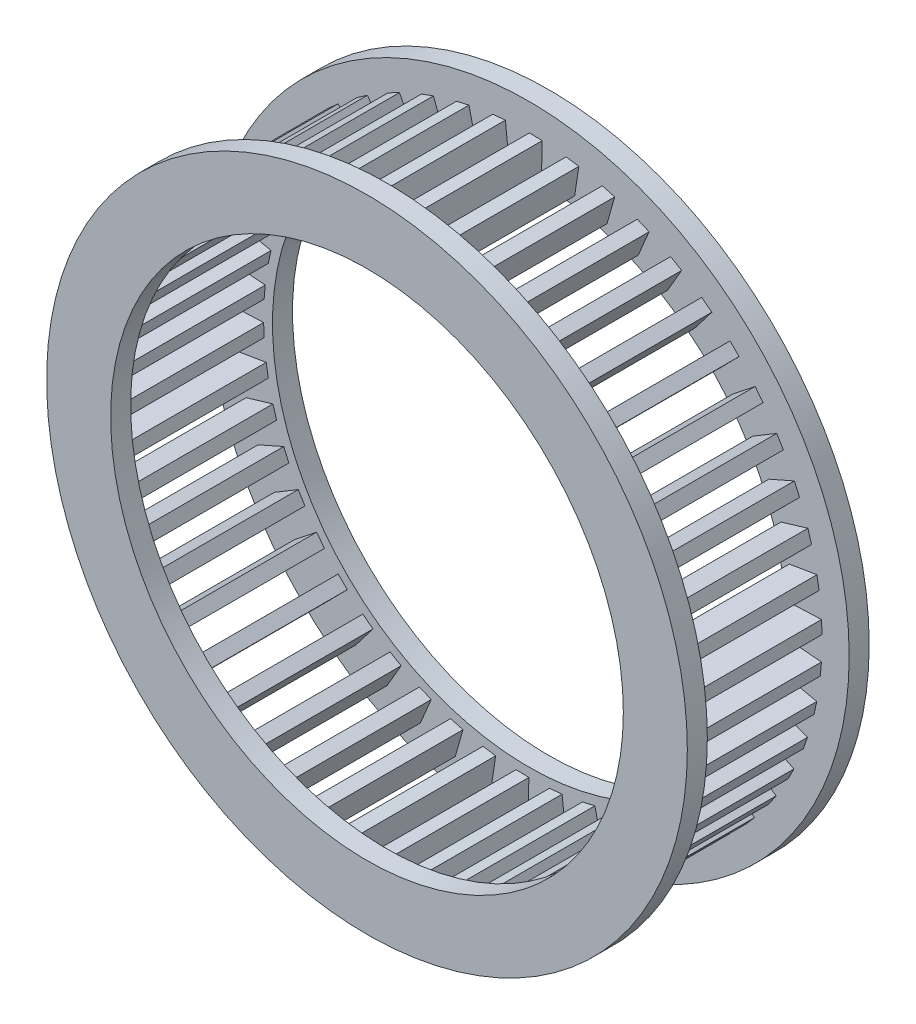
SolidWorks part; units mm, degrees
ref_plane "Спереди" through (0, 0, 0) normal (0, 0, 1) x (1, 0, 0)
ref_plane "Сверху" through (0, 0, 0) normal (0, 1, 0) x (1, 0, 0)
ref_plane "Справа" through (0, 0, 0) normal (1, 0, 0) x (0, 0, -1)
sketch "Эскиз1" plane through (0, 0, 0) normal (0, 0, 1) x (1, 0, 0)
  line L0 (56.0871, 0.8311) -> (62.0057, 1.0618)
  line L1 (62.0057, 1.0618) -> (61.9002, 3.7675)
  line L2 (61.9002, 3.7675) -> (55.9817, 3.5368)
  line L3 (55.9817, 3.5368) -> (56.0871, 0.8311)
  line L4 (55.5407, 7.8542) -> (61.3837, 8.8248)
  line L5 (61.3837, 8.8248) -> (60.9399, 11.4959)
  line L6 (60.9399, 11.4959) -> (55.0969, 10.5253)
  line L7 (55.0969, 10.5253) -> (55.5407, 7.8542)
  line L8 (54.1183, 14.7533) -> (59.7936, 16.4487)
  line L9 (59.7936, 16.4487) -> (59.0186, 19.0431)
  line L10 (59.0186, 19.0431) -> (53.3433, 17.3477)
  line L11 (53.3433, 17.3477) -> (54.1183, 14.7533)
  line L12 (51.8425, 21.4198) -> (57.2605, 23.8131)
  line L13 (57.2605, 23.8131) -> (56.1665, 26.2899)
  line L14 (56.1665, 26.2899) -> (50.7484, 23.8966)
  line L15 (50.7484, 23.8966) -> (51.8425, 21.4198)
  line L16 (48.7491, 27.7485) -> (53.8245, 30.802)
  line L17 (53.8245, 30.802) -> (52.4286, 33.1221)
  line L18 (52.4286, 33.1221) -> (47.3532, 30.0687)
  line L19 (47.3532, 30.0687) -> (48.7491, 27.7485)
  line L20 (44.8869, 33.6396) -> (49.5395, 37.3051)
  line L21 (49.5395, 37.3051) -> (47.8639, 39.432)
  line L22 (47.8639, 39.432) -> (43.2112, 35.7665)
  line L23 (43.2112, 35.7665) -> (44.8869, 33.6396)
  line L24 (40.3168, 39.0001) -> (44.4733, 43.2199)
  line L25 (44.4733, 43.2199) -> (42.5443, 45.12)
  line L26 (42.5443, 45.12) -> (38.3878, 40.9003)
  line L27 (38.3878, 40.9003) -> (40.3168, 39.0001)
  line L28 (35.1109, 43.7457) -> (38.7058, 48.453)
  line L29 (38.7058, 48.453) -> (36.5538, 50.0964)
  line L30 (36.5538, 50.0964) -> (32.9589, 45.389)
  line L31 (32.9589, 45.389) -> (35.1109, 43.7457)
  line L32 (29.3512, 47.8013) -> (32.3278, 52.9221)
  line L33 (32.3278, 52.9221) -> (29.9868, 54.2828)
  line L34 (29.9868, 54.2828) -> (27.0103, 49.162)
  line L35 (27.0103, 49.162) -> (29.3512, 47.8013)
  line L36 (23.1287, 51.103) -> (25.44, 56.5565)
  line L37 (25.44, 56.5565) -> (22.9469, 57.6131)
  line L38 (22.9469, 57.6131) -> (20.6356, 52.1596)
  line L39 (20.6356, 52.1596) -> (23.1287, 51.103)
  line L40 (16.5414, 53.5988) -> (18.151, 59.299)
  line L41 (18.151, 59.299) -> (15.5452, 60.0348)
  line L42 (15.5452, 60.0348) -> (13.9356, 54.3346)
  line L43 (13.9356, 54.3346) -> (16.5414, 53.5988)
  line L44 (9.6933, 55.2494) -> (10.5757, 61.1064)
  line L45 (10.5757, 61.1064) -> (7.8982, 61.5098)
  line L46 (7.8982, 61.5098) -> (7.0158, 55.6528)
  line L47 (7.0158, 55.6528) -> (9.6933, 55.2494)
  line L48 (2.6922, 56.0286) -> (2.8336, 61.95)
  line L49 (2.8336, 61.95) -> (0.1267, 62.0147)
  line L50 (0.1267, 62.0147) -> (-0.0147, 56.0933)
  line L51 (-0.0147, 56.0933) -> (2.6922, 56.0286)
  line L52 (-4.3512, 55.9242) -> (-4.9531, 61.8167)
  line L53 (-4.9531, 61.8167) -> (-7.6468, 61.5415)
  line L54 (-7.6468, 61.5415) -> (-7.0449, 55.6491)
  line L55 (-7.0449, 55.6491) -> (-4.3512, 55.9242)
  line L56 (-11.3261, 54.9379) -> (-12.6617, 60.7084)
  line L57 (-12.6617, 60.7084) -> (-15.2997, 60.0979)
  line L58 (-15.2997, 60.0979) -> (-13.9641, 54.3273)
  line L59 (-13.9641, 54.3273) -> (-11.3261, 54.9379)
  line L60 (-18.1223, 53.0852) -> (-20.1707, 58.6428)
  line L61 (-20.1707, 58.6428) -> (-22.7113, 57.7064)
  line L62 (-22.7113, 57.7064) -> (-20.663, 52.1488)
  line L63 (-20.663, 52.1488) -> (-18.1223, 53.0852)
  line L64 (-24.6328, 50.3952) -> (-27.3615, 55.6523)
  line L65 (-27.3615, 55.6523) -> (-29.7647, 54.4049)
  line L66 (-29.7647, 54.4049) -> (-27.036, 49.1478)
  line L67 (-27.036, 49.1478) -> (-24.6328, 50.3952)
  line L68 (-30.7547, 46.9106) -> (-34.1208, 51.7842)
  line L69 (-34.1208, 51.7842) -> (-36.3488, 50.2454)
  line L70 (-36.3488, 50.2454) -> (-32.9827, 45.3718)
  line L71 (-32.9827, 45.3718) -> (-30.7547, 46.9106)
  line L72 (-36.3917, 42.6861) -> (-40.3421, 47.0994)
  line L73 (-40.3421, 47.0994) -> (-42.3596, 45.2935)
  line L74 (-42.3596, 45.2935) -> (-38.4092, 40.8802)
  line L75 (-38.4092, 40.8802) -> (-36.3917, 42.6861)
  line L76 (-41.4547, 37.7884) -> (-45.9271, 41.6718)
  line L77 (-45.9271, 41.6718) -> (-47.7023, 39.6273)
  line L78 (-47.7023, 39.6273) -> (-43.23, 35.7439)
  line L79 (-43.23, 35.7439) -> (-41.4547, 37.7884)
  line L80 (-45.864, 32.2948) -> (-50.7878, 35.587)
  line L81 (-50.7878, 35.587) -> (-52.2928, 33.3361)
  line L82 (-52.2928, 33.3361) -> (-47.369, 30.0439)
  line L83 (-47.369, 30.0439) -> (-45.864, 32.2948)
  line L84 (-49.5499, 26.2918) -> (-54.8475, 28.941)
  line L85 (-54.8475, 28.941) -> (-56.0586, 26.5192)
  line L86 (-56.0586, 26.5192) -> (-50.761, 23.8701)
  line L87 (-50.761, 23.8701) -> (-49.5499, 26.2918)
  line L88 (-52.4544, 19.8743) -> (-58.0423, 21.8386)
  line L89 (-58.0423, 21.8386) -> (-58.9403, 19.2841)
  line L90 (-58.9403, 19.2841) -> (-53.3524, 17.3198)
  line L91 (-53.3524, 17.3198) -> (-52.4544, 19.8743)
  line L92 (-54.5317, 13.1433) -> (-60.3217, 14.3917)
  line L93 (-60.3217, 14.3917) -> (-60.8925, 11.7449)
  line L94 (-60.8925, 11.7449) -> (-55.1024, 10.4964)
  line L95 (-55.1024, 10.4964) -> (-54.5317, 13.1433)
  line L96 (-55.749, 6.205) -> (-61.6498, 6.7179)
  line L97 (-61.6498, 6.7179) -> (-61.8843, 4.0204)
  line L98 (-61.8843, 4.0204) -> (-55.9835, 3.5075)
  line L99 (-55.9835, 3.5075) -> (-55.749, 6.205)
  line L100 (-56.0871, -0.8311) -> (-62.0057, -1.0618)
  line L101 (-62.0057, -1.0618) -> (-61.9002, -3.7675)
  line L102 (-61.9002, -3.7675) -> (-55.9817, -3.5368)
  line L103 (-55.9817, -3.5368) -> (-56.0871, -0.8311)
  line L104 (-55.5407, -7.8542) -> (-61.3837, -8.8248)
  line L105 (-61.3837, -8.8248) -> (-60.9399, -11.4959)
  line L106 (-60.9399, -11.4959) -> (-55.0969, -10.5253)
  line L107 (-55.0969, -10.5253) -> (-55.5407, -7.8542)
  line L108 (-54.1183, -14.7533) -> (-59.7936, -16.4487)
  line L109 (-59.7936, -16.4487) -> (-59.0186, -19.0431)
  line L110 (-59.0186, -19.0431) -> (-53.3433, -17.3477)
  line L111 (-53.3433, -17.3477) -> (-54.1183, -14.7533)
  line L112 (-51.8425, -21.4198) -> (-57.2605, -23.8131)
  line L113 (-57.2605, -23.8131) -> (-56.1665, -26.2899)
  line L114 (-56.1665, -26.2899) -> (-50.7484, -23.8966)
  line L115 (-50.7484, -23.8966) -> (-51.8425, -21.4198)
  line L116 (-48.7491, -27.7485) -> (-53.8245, -30.802)
  line L117 (-53.8245, -30.802) -> (-52.4286, -33.1221)
  line L118 (-52.4286, -33.1221) -> (-47.3532, -30.0687)
  line L119 (-47.3532, -30.0687) -> (-48.7491, -27.7485)
  line L120 (-44.8869, -33.6396) -> (-49.5395, -37.3051)
  line L121 (-49.5395, -37.3051) -> (-47.8639, -39.432)
  line L122 (-47.8639, -39.432) -> (-43.2112, -35.7665)
  line L123 (-43.2112, -35.7665) -> (-44.8869, -33.6396)
  line L124 (-40.3168, -39.0001) -> (-44.4733, -43.2199)
  line L125 (-44.4733, -43.2199) -> (-42.5443, -45.12)
  line L126 (-42.5443, -45.12) -> (-38.3878, -40.9003)
  line L127 (-38.3878, -40.9003) -> (-40.3168, -39.0001)
  line L128 (-35.1109, -43.7457) -> (-38.7058, -48.453)
  line L129 (-38.7058, -48.453) -> (-36.5538, -50.0964)
  line L130 (-36.5538, -50.0964) -> (-32.9589, -45.389)
  line L131 (-32.9589, -45.389) -> (-35.1109, -43.7457)
  line L132 (-29.3512, -47.8013) -> (-32.3278, -52.9221)
  line L133 (-32.3278, -52.9221) -> (-29.9868, -54.2828)
  line L134 (-29.9868, -54.2828) -> (-27.0103, -49.162)
  line L135 (-27.0103, -49.162) -> (-29.3512, -47.8013)
  line L136 (-23.1287, -51.103) -> (-25.44, -56.5565)
  line L137 (-25.44, -56.5565) -> (-22.9469, -57.6131)
  line L138 (-22.9469, -57.6131) -> (-20.6356, -52.1596)
  line L139 (-20.6356, -52.1596) -> (-23.1287, -51.103)
  line L140 (-16.5414, -53.5988) -> (-18.151, -59.299)
  line L141 (-18.151, -59.299) -> (-15.5452, -60.0348)
  line L142 (-15.5452, -60.0348) -> (-13.9356, -54.3346)
  line L143 (-13.9356, -54.3346) -> (-16.5414, -53.5988)
  line L144 (-9.6933, -55.2494) -> (-10.5757, -61.1064)
  line L145 (-10.5757, -61.1064) -> (-7.8982, -61.5098)
  line L146 (-7.8982, -61.5098) -> (-7.0158, -55.6528)
  line L147 (-7.0158, -55.6528) -> (-9.6933, -55.2494)
  line L148 (-2.6922, -56.0286) -> (-2.8336, -61.95)
  line L149 (-2.8336, -61.95) -> (-0.1267, -62.0147)
  line L150 (-0.1267, -62.0147) -> (0.0147, -56.0933)
  line L151 (0.0147, -56.0933) -> (-2.6922, -56.0286)
  line L152 (4.3512, -55.9242) -> (4.9531, -61.8167)
  line L153 (4.9531, -61.8167) -> (7.6468, -61.5415)
  line L154 (7.6468, -61.5415) -> (7.0449, -55.6491)
  line L155 (7.0449, -55.6491) -> (4.3512, -55.9242)
  line L156 (11.3261, -54.9379) -> (12.6617, -60.7084)
  line L157 (12.6617, -60.7084) -> (15.2997, -60.0979)
  line L158 (15.2997, -60.0979) -> (13.9641, -54.3273)
  line L159 (13.9641, -54.3273) -> (11.3261, -54.9379)
  line L160 (18.1223, -53.0852) -> (20.1707, -58.6428)
  line L161 (20.1707, -58.6428) -> (22.7113, -57.7064)
  line L162 (22.7113, -57.7064) -> (20.663, -52.1488)
  line L163 (20.663, -52.1488) -> (18.1223, -53.0852)
  line L164 (24.6328, -50.3952) -> (27.3615, -55.6523)
  line L165 (27.3615, -55.6523) -> (29.7647, -54.4049)
  line L166 (29.7647, -54.4049) -> (27.036, -49.1478)
  line L167 (27.036, -49.1478) -> (24.6328, -50.3952)
  line L168 (30.7547, -46.9106) -> (34.1208, -51.7842)
  line L169 (34.1208, -51.7842) -> (36.3488, -50.2454)
  line L170 (36.3488, -50.2454) -> (32.9827, -45.3718)
  line L171 (32.9827, -45.3718) -> (30.7547, -46.9106)
  line L172 (36.3917, -42.6861) -> (40.3421, -47.0994)
  line L173 (40.3421, -47.0994) -> (42.3596, -45.2935)
  line L174 (42.3596, -45.2935) -> (38.4092, -40.8802)
  line L175 (38.4092, -40.8802) -> (36.3917, -42.6861)
  line L176 (41.4547, -37.7884) -> (45.9271, -41.6718)
  line L177 (45.9271, -41.6718) -> (47.7023, -39.6273)
  line L178 (47.7023, -39.6273) -> (43.23, -35.7439)
  line L179 (43.23, -35.7439) -> (41.4547, -37.7884)
  line L180 (45.864, -32.2948) -> (50.7878, -35.587)
  line L181 (50.7878, -35.587) -> (52.2928, -33.3361)
  line L182 (52.2928, -33.3361) -> (47.369, -30.0439)
  line L183 (47.369, -30.0439) -> (45.864, -32.2948)
  line L184 (49.5499, -26.2918) -> (54.8475, -28.941)
  line L185 (54.8475, -28.941) -> (56.0586, -26.5192)
  line L186 (56.0586, -26.5192) -> (50.761, -23.8701)
  line L187 (50.761, -23.8701) -> (49.5499, -26.2918)
  line L188 (52.4544, -19.8743) -> (58.0423, -21.8386)
  line L189 (58.0423, -21.8386) -> (58.9403, -19.2841)
  line L190 (58.9403, -19.2841) -> (53.3524, -17.3198)
  line L191 (53.3524, -17.3198) -> (52.4544, -19.8743)
  line L192 (54.5317, -13.1433) -> (60.3217, -14.3917)
  line L193 (60.3217, -14.3917) -> (60.8925, -11.7449)
  line L194 (60.8925, -11.7449) -> (55.1024, -10.4964)
  line L195 (55.1024, -10.4964) -> (54.5317, -13.1433)
  line L196 (55.749, -6.205) -> (61.6498, -6.7179)
  line L197 (61.6498, -6.7179) -> (61.8843, -4.0204)
  line L198 (61.8843, -4.0204) -> (55.9835, -3.5075)
  line L199 (55.9835, -3.5075) -> (55.749, -6.205)
extrude "Cage_50_bars" add sketch "Эскиз1" along normal blind 30.2 from offset 15.1 separate body offset against normal yes
sketch "Эскиз2" plane through (0, 0, 0) normal (0, 0, 1) x (1, 0, 0)
  circle A0 centre (0, 0) radius 67.7538
  circle A1 centre (0, 0) radius 54.2154
extrude "Cage_ring_right" add sketch "Эскиз2" along normal blind 4.2308 from offset 15
sketch "Эскиз3" plane through (0, 0, 0) normal (0, 0, 1) x (1, 0, 0)
  circle A0 centre (0, 0) radius 67.7538
  circle A1 centre (0, 0) radius 54.2154
extrude "Cage_ring_left" add sketch "Эскиз3" along normal blind 4.2308 from offset 19.2308 offset against normal yes
